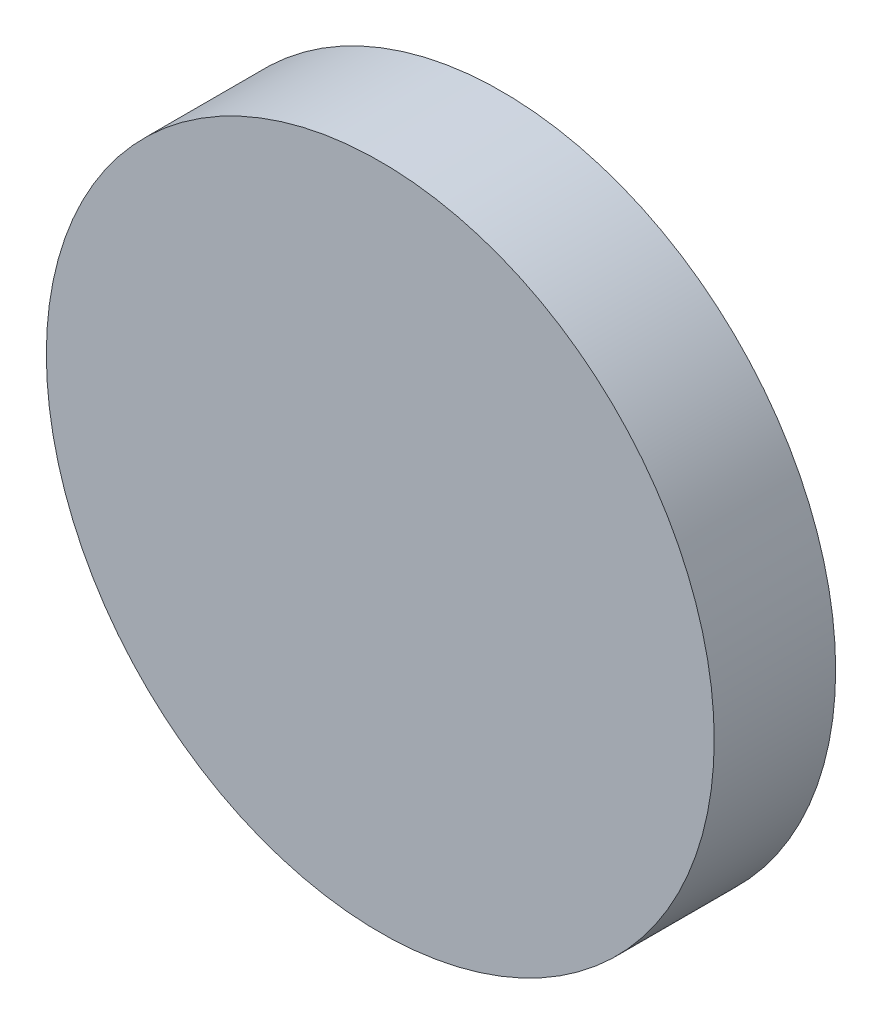
SolidWorks part; units mm, degrees
ref_plane "Front Plane" through (0, 0, 0) normal (0, 0, 1) x (1, 0, 0)
ref_plane "Top Plane" through (0, 0, 0) normal (0, 1, 0) x (1, 0, 0)
ref_plane "Right Plane" through (0, 0, 0) normal (1, 0, 0) x (0, 0, -1)
sketch "Sketch1" plane through (0, 0, 0) normal (0, 0, 1) x (1, 0, 0)
  circle A0 centre (0, 0) radius 27.5
  dimension "D1" = 55
extrude "Boss-Extrude1" add sketch "Sketch1" along normal blind 10
